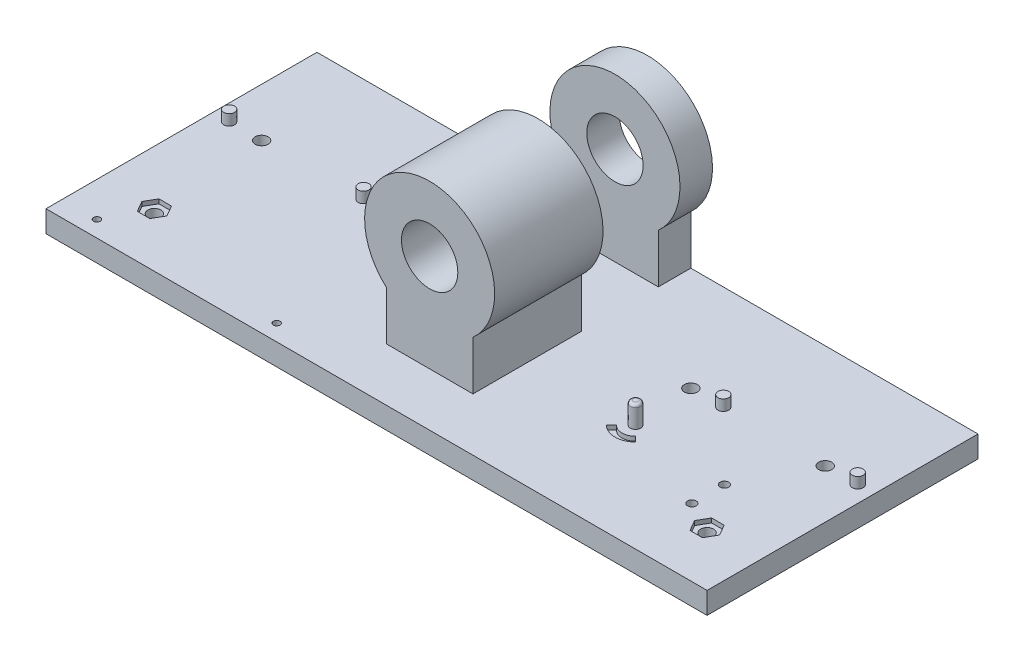
SolidWorks part; units mm, degrees
ref_plane "Front Plane" through (0, 0, 0) normal (0, 0, 1) x (1, 0, 0)
ref_plane "Top Plane" through (0, 0, 0) normal (0, 1, 0) x (1, 0, 0)
ref_plane "Right Plane" through (0, 0, 0) normal (1, 0, 0) x (0, 0, -1)
sketch "Sketch1" plane through (0, 0, 0) normal (0, 1, 0) x (1, 0, 0)
  line L0 (152.5, 125) -> (152.5, 0) construction
  line L1 (0, 0) -> (305, 0)
  line L2 (0, 0) -> (0, 125)
  line L3 (0, 125) -> (305, 125)
  line L4 (305, 0) -> (305, 125)
  line L5 (25, 100) -> (280, 100) construction
  line L6 (280, 25) -> (280, 100) construction
  line L7 (25, 25) -> (280, 25) construction
  line L8 (25, 25) -> (25, 100) construction
  line L9 (152.5, 62.5) -> (25, 62.5) construction
  line L10 (30.7735, 100) -> (27.8868, 105) construction
  line L11 (27.8868, 105) -> (22.1132, 105) construction
  line L12 (22.1132, 105) -> (19.2265, 100) construction
  line L13 (19.2265, 100) -> (22.1132, 95) construction
  line L14 (22.1132, 95) -> (27.8868, 95) construction
  line L15 (27.8868, 95) -> (30.7735, 100) construction
  line L16 (27.8868, 30) -> (30.7735, 25) construction
  line L17 (22.1132, 30) -> (27.8868, 30) construction
  line L18 (19.2265, 25) -> (22.1132, 30) construction
  line L19 (22.1132, 20) -> (19.2265, 25) construction
  line L20 (27.8868, 20) -> (22.1132, 20) construction
  line L21 (30.7735, 25) -> (27.8868, 20) construction
  line L22 (282.8868, 30) -> (277.1132, 30) construction
  line L23 (285.7735, 25) -> (282.8868, 30) construction
  line L24 (282.8868, 20) -> (285.7735, 25) construction
  line L25 (277.1132, 20) -> (282.8868, 20) construction
  line L26 (274.2265, 25) -> (277.1132, 20) construction
  line L27 (277.1132, 30) -> (274.2265, 25) construction
  line L28 (277.1132, 95) -> (274.2265, 100) construction
  line L29 (282.8868, 95) -> (277.1132, 95) construction
  line L30 (285.7735, 100) -> (282.8868, 95) construction
  line L31 (282.8868, 105) -> (285.7735, 100) construction
  line L32 (277.1132, 105) -> (282.8868, 105) construction
  line L33 (274.2265, 100) -> (277.1132, 105) construction
  line L34 (172.5, 75) -> (172.5, 125) construction
  line L35 (132.5, 0) -> (172.5, 0) construction
  line L36 (132.5, 0) -> (132.5, 125) construction
  line L37 (132.5, 125) -> (172.5, 125) construction
  line L38 (172.5, 0) -> (172.5, 125) construction
  line L39 (132.5, 75) -> (172.5, 75) construction
  line L40 (132.5, 75) -> (132.5, 25) construction
  line L41 (132.5, 25) -> (172.5, 25) construction
  line L42 (172.5, 75) -> (172.5, 25) construction
  line L50 (305, 14.5) -> (253.3, 14.5) construction
  line L51 (0, 84.5) -> (15, 69.5) construction
  line L52 (132.5, 75) -> (117.5, 60) construction
  line L53 (117.5, 60) -> (117.5, 85) construction
  line L54 (0, 125) -> (108, 125) construction
  line L55 (0, 125) -> (0, 84.5) construction
  line L56 (0, 84.5) -> (108, 84.5) construction
  line L57 (108, 125) -> (108, 84.5) construction
  line L58 (15, 69.5) -> (15, 84.5) construction
  line L59 (30, 84.5) -> (0, 84.5) construction
  line L60 (30, 84.5) -> (30, 69.5) construction
  line L61 (30, 69.5) -> (0, 69.5) construction
  line L62 (0, 84.5) -> (0, 69.5) construction
  line L63 (92, 84.5) -> (92, 69.5) construction
  line L64 (62, 0) -> (62, 125) construction
  line L65 (253.3, 14.5) -> (253.3, 0) construction
  line L66 (253.3, 38.75) -> (280.2, 38.75) construction
  line L67 (253.3, 14.5) -> (280.2, 14.5) construction
  line L68 (253.3, 14.5) -> (253.3, 63) construction
  line L69 (253.3, 63) -> (280.2, 63) construction
  line L70 (280.2, 14.5) -> (280.2, 63) construction
  line L71 (266.75, 31.25) -> (266.75, 38.75) construction
  circle A1 centre (25, 100) radius 5 construction
  circle A3 centre (280, 25) radius 3
  circle A4 centre (25, 25) radius 3
  circle A8 centre (117.5, 60) radius 3
  circle A9 centre (117.5, 85) radius 3
  circle A10 centre (7.5, 77) radius 3 construction
  circle A11 centre (22.5, 77) radius 3
  circle A12 centre (69.5, 77) radius 3 construction
  circle A13 centre (84.5, 77) radius 3
  circle A14 centre (220.5, 77) radius 3
  circle A15 centre (235.5, 77) radius 3 construction
  circle A16 centre (282.5, 77) radius 3
  circle A17 centre (297.5, 77) radius 3 construction
  circle A18 centre (266.75, 31.25) radius 2
  circle A19 centre (266.75, 46.25) radius 2
  dimension "D3" = 6
  dimension "D22" = 4
  dimension "D1" = 305
  dimension "D2" = 125
  dimension "D5" = 10
  dimension "D6" = 40
  dimension "D8" = 50
  dimension "D12" = 15
  dimension "D7" = 40.5
  dimension "D9" = 108
  dimension "D10" = 15
  dimension "D11" = 30
  dimension "D15" = 62
  dimension "D16" = 15
  dimension "D17" = 25
  dimension "D18" = 51.7
  dimension "D19" = 14.5
  dimension "D20" = 26.9
  dimension "D21" = 48.5
  dimension "D23" = 7.5
  dimension "D4" = 25
  dimension "D13" = 2
  dimension "D14" = 2
extrude "Boss-Extrude1" add sketch "Sketch1" along normal blind 10
sketch "Sketch7" plane through (0, 10, 0) normal (0, 1, 0) x (1, 0, 0)
  line L0 (0, 0) -> (305, 0) construction
  line L1 (132.5, 24.5) -> (172.5, 24.5)
  line L2 (132.5, 24.5) -> (132.5, 74.5)
  line L3 (132.5, 74.5) -> (172.5, 74.5)
  line L4 (172.5, 24.5) -> (172.5, 74.5)
  line L5 (152.5, 0) -> (152.5, 125) construction
  line L6 (305, 125) -> (0, 125) construction
  line L18 (132.5, 110) -> (172.5, 110)
  line L19 (132.5, 110) -> (132.5, 125)
  line L20 (132.5, 125) -> (172.5, 125)
  line L21 (172.5, 110) -> (172.5, 125)
  point P11 (152.5, 74.5)
  point P20 (152.5, 110)
  dimension "D1" = 40
  dimension "D2" = 50
  dimension "D4" = 15
  dimension "D3" = 35.5
extrude "Boss-Extrude2" add sketch "Sketch7" along normal blind 22.6393
sketch "Sketch11" plane through (0, 0, -24.5) normal (0, 0, 1) x (1, 0, 0)
  circle A0 centre (152.5, 55) radius 30
  circle A1 centre (152.5, 55) radius 13
  dimension "D1" = 60
  dimension "D2" = 26
extrude "Boss-Extrude3" add sketch "Sketch11" against normal up to surface (100.5 mm away) up to face at (152.5, 13.1598, -125)
ref_plane "Plane1" through (0, 0, -62.5) normal (0, 0, 1) x (1, 0, 0)
sketch "Sketch12" plane through (305, 0, 0) normal (1, 0, 0) x (0, 0, -1)
  line L0 (125, 85) -> (24.5, 85) construction
  line L1 (74.5, 10) -> (110, 10)
  line L2 (74.5, 10) -> (74.5, 85)
  line L3 (74.5, 85) -> (110, 85)
  line L4 (110, 10) -> (110, 85)
  line L6 (110, 32.6393) -> (110, 10) construction
extrude "Cut-Extrude2" cut sketch "Sketch12" against normal through all
sketch "Sketch13" plane through (0, 10, 0) normal (0, 1, 0) x (1, 0, 0)
  line L0 (222.5, 49.5) -> (172.5, 49.5) construction
  line L1 (172.5, 24.5) -> (172.5, 74.5) construction
  circle A1 centre (222.5, 49.5) radius 2.4
  dimension "D1" = 4.8
  dimension "D2" = 50
extrude "Boss-Extrude4" add sketch "Sketch13" along normal blind 10
sketch "Sketch6" plane through (0, 10, 0) normal (0, 1, 0) x (1, 0, 0)
  line L0 (152.5, 125) -> (152.5, 0) construction
  line L7 (215.7825, 42.7825) -> (218.0806, 45.0806)
  line L8 (0, 0) -> (305, 0) construction
  line L9 (152.5, 62.5) -> (0, 62.5) construction
  line L10 (0, 125) -> (0, 0) construction
  line L29 (27.8868, 30) -> (30.7735, 25)
  line L30 (274.2265, 25) -> (277.1132, 20)
  line L31 (277.1132, 20) -> (282.8868, 20)
  line L32 (282.8868, 20) -> (285.7735, 25)
  line L33 (285.7735, 25) -> (282.8868, 30)
  line L34 (282.8868, 30) -> (277.1132, 30)
  line L35 (277.1132, 30) -> (274.2265, 25)
  line L36 (22.1132, 30) -> (27.8868, 30)
  line L37 (19.2265, 25) -> (22.1132, 30)
  line L38 (22.1132, 20) -> (19.2265, 25)
  line L39 (27.8868, 20) -> (22.1132, 20)
  line L40 (30.7735, 25) -> (27.8868, 20)
  line L41 (231.3388, 40.6612) -> (213.6612, 58.3388) construction
  line L42 (213.6612, 40.6612) -> (231.3388, 58.3388) construction
  line L43 (222.5, 49.5) -> (222.5, 37) construction
  line L44 (213.6612, 40.6612) -> (222.5, 37) construction
  line L45 (222.5, 37) -> (231.3388, 40.6612) construction
  line L46 (229.2175, 42.7825) -> (226.9194, 45.0806)
  circle A0 centre (280, 25) radius 5 construction
  circle A1 centre (222.5, 49.5) radius 12.5 construction
  circle A2 centre (222.5, 49.5) radius 9.5 construction
  circle A3 centre (222.5, 49.5) radius 6.25 construction
  arc A4 (218.0806, 45.0806) -> (226.9194, 45.0806) centre (222.5, 49.5) ccw
  arc A5 (215.7825, 42.7825) -> (229.2175, 42.7825) centre (222.5, 49.5) ccw
  dimension "D2" = 25
  dimension "D4" = 12.5
  dimension "D1" = 10
  dimension "D3" = 3
extrude "Cut-Extrude1" cut sketch "Sketch6" against normal blind 2
fillet "Fillet1" radius 1.3 1 edges at (222.5, 20, -47.1)
sketch "Sketch15" plane through (0, 10, 0) normal (0, 1, 0) x (1, 0, 0)
  line L0 (69.5, 77) -> (7.5, 77) construction
  line L1 (38.5, 77) -> (38.5, 84.5) construction
  line L2 (0, 84.5) -> (108, 84.5) construction
  line L3 (152.5, 125) -> (152.5, 0) construction
  circle A1 centre (69.5, 77) radius 2.5
  circle A2 centre (7.5, 77) radius 2.5
  circle A3 centre (7.5, 77) radius 2.5
  circle A4 centre (235.5, 77) radius 2.5
  circle A5 centre (297.5, 77) radius 2.5
  dimension "D1" = 0.5
extrude "Boss-Extrude5" add sketch "Sketch15" along normal blind 5
chamfer "Chamfer1" distance 3.3 angle 45 6 edges at (282.5, 0, -74) (220.5, 0, -74) (84.5, 0, -80) (22.5, 0, -80) (117.5, 0, -57) (117.5, 0, -82)
fillet "Fillet2" [suppressed] radius 0.5
fillet "Fillet3" [suppressed] radius 10
sketch "Sketch16" plane through (0, 10, 0) normal (0, 1, 0) x (1, 0, 0)
  line L0 (0, 0) -> (305, 0) construction
  line L1 (0, 125) -> (0, 0) construction
  circle A0 centre (16, 7.5) radius 1.55
  circle A1 centre (98.95, 7.5) radius 1.55
  point P6 (0, 0)
  dimension "D1" = 3.1
  dimension "D2" = 7.5
  dimension "D3" = 82.95
  dimension "D4" = 16
extrude "Cut-Extrude3" cut sketch "Sketch16" against normal through all
equation "\"joint_width\"=4"
equation "\"short_base_length\"=12.5"
equation "\"D2@Sketch1\"=\"short_base_length\""
equation "\"outer_diam_main_joint\"=6"
equation "\"D1@Sketch11\"=\"outer_diam_main_joint\""
equation "\"D1@Sketch7\"=\"outer_diam_main_joint\"-2"
equation "\"D1@Boss-Extrude2\"=(\"outer_diam_main_joint\"/2)+1.5cm-sqr((\"outer_diam_main_joint\"/2)^2-((\"outer_diam_main_joint\"-2)/2)^2)"
equation "\"D6@Sketch1\"=\"outer_diam_main_joint\"-2"
equation "\"pulleyside\"=1.5"
